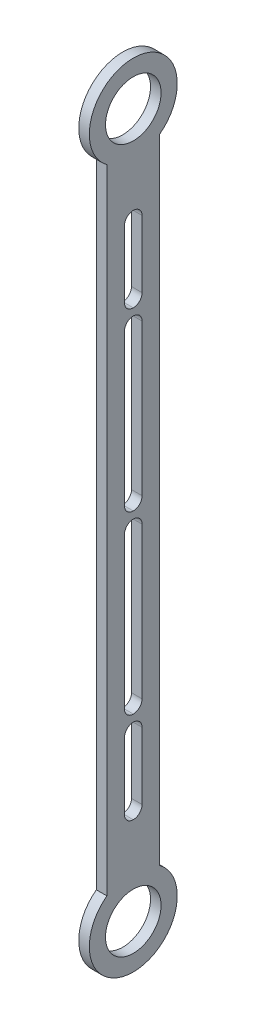
SolidWorks part; units mm, degrees
ref_plane "Front Plane" through (0, 0, 0) normal (0, 0, 1) x (1, 0, 0)
ref_plane "Top Plane" through (0, 0, 0) normal (0, 1, 0) x (1, 0, 0)
ref_plane "Right Plane" through (0, 0, 0) normal (1, 0, 0) x (0, 0, -1)
sketch "Sketch1" plane through (0, 0, 0) normal (1, 0, 0) x (0, 0, -1)
  line L0 (12.5, 0) -> (12.5, 200)
  line L1 (-12.5, 200) -> (-12.5, 0)
  line L2 (7.5, 190) -> (7.5, 10)
  line L3 (-7.5, 10) -> (-7.5, 190)
  circle A0 centre (0, 0) radius 7.9
  circle A1 centre (0, 200) radius 7.9
  circle A2 centre (0, 200) radius 12.5
  circle A3 centre (0, 0) radius 12.5
  dimension "D1" = 15.8
  dimension "D2" = 15.8
  dimension "D3" = 200
  dimension "D4" = 25
  dimension "D5" = 25
  dimension "D6" = 5
  dimension "D7" = 5
extrude "Boss-Extrude1" add sketch "Sketch1" along normal blind 3 contours A3 L0 A2 L1 | A2 A1 | A3 A0
sketch "Sketch2" plane through (3, 0, 0) normal (1, 0, 0) x (0, 0, -1)
  line L0 (0, 192.1) -> (0, 7.9) construction
  line L1 (0, 157.1) -> (-4.2194, 100)
  line L2 (-4.2194, 100) -> (0, 42.9)
  line L3 (0, 157.1) -> (4.2194, 100)
  line L4 (4.2194, 100) -> (0, 42.9)
  circle A0 centre (0, 200) radius 7.9 construction
  circle A1 centre (0, 0) radius 7.9 construction
  dimension "D1" = 35
  dimension "D2" = 35
extrude "Cut-Extrude1" [suppressed] cut sketch "Sketch2" against normal through all
fillet "Fillet1" [suppressed] radius 0.5
sketch "Sketch3" plane through (3, 0, 0) normal (1, 0, 0) x (0, 0, -1)
  line L0 (0, 0) -> (0, 7.9) construction
  line L1 (-2.5, 175) -> (2.5, 175)
  line L2 (-2.5, 175) -> (-2.5, 25)
  line L3 (-2.5, 25) -> (2.5, 25)
  line L4 (2.5, 175) -> (2.5, 25)
  line L5 (0, 25) -> (0, 26.3227) construction
  circle A0 centre (0, 0) radius 7.9 construction
  circle A1 centre (0, 200) radius 7.9 construction
  dimension "D1" = 25
  dimension "D2" = 25
  dimension "D3" = 5
extrude "Cut-Extrude2" cut sketch "Sketch3" against normal through all
fillet "Fillet2" radius 2.5 4 edges at (1.5, 175, 2.5) (1.5, 175, -2.5) (1.5, 25, 2.5) (1.5, 25, -2.5)
sketch "Sketch4" plane through (3, 0, 0) normal (1, 0, 0) x (0, 0, -1)
  line L0 (2.5, 27.5) -> (2.5, 172.5) construction
  line L1 (-2.5, 101.007) -> (2.5, 101.007)
  line L2 (-2.5, 101.007) -> (-2.5, 99.007)
  line L3 (-2.5, 99.007) -> (2.5, 99.007)
  line L4 (2.5, 101.007) -> (2.5, 99.007)
  line L5 (-2.5, 172.5) -> (-2.5, 27.5) construction
  line L6 (-2.5, 100.007) -> (2.5, 100.007) construction
  line L7 (2.5, 100.007) -> (2.5, 100) construction
  line L8 (2.5, 100) -> (-2.5, 100) construction
  line L9 (-2.5, 51.007) -> (2.5, 51.007)
  line L10 (-2.5, 49.007) -> (2.5, 49.007)
  line L11 (-2.5, 51.007) -> (-2.5, 49.007)
  line L12 (2.5, 51.007) -> (2.5, 49.007)
  line L13 (-2.5, 149.007) -> (2.5, 149.007)
  line L14 (-2.5, 151.007) -> (2.5, 151.007)
  line L15 (-2.5, 151.007) -> (-2.5, 149.007)
  line L16 (2.5, 151.007) -> (2.5, 149.007)
  dimension "D1" = 2
  dimension "D2" = 2
  dimension "D3" = 2
extrude "Boss-Extrude2" add sketch "Sketch4" against normal blind 3
fillet "Fillet3" radius 2.5 12 edges at (1.5, 101.007, -2.5) (1.5, 101.007, 2.5) (1.5, 51.007, 2.5) (1.5, 51.007, -2.5) (1.5, 49.007, 2.5) (1.5, 49.007, -2.5) (1.5, 99.007, -2.5) (1.5, 99.007, 2.5) (1.5, 149.007, 2.5) (1.5, 149.007, -2.5) (1.5, 151.007, 2.5) (1.5, 151.007, -2.5)
